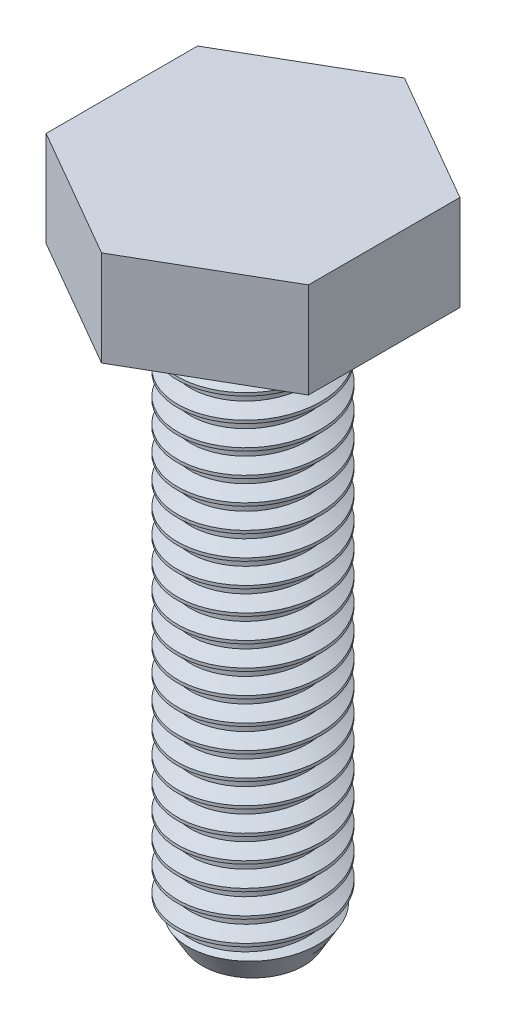
SolidWorks part; units mm, degrees
material "Alloy Steel"
ref_plane "Front Plane" through (0, 0, 0) normal (0, 0, 1) x (1, 0, 0)
ref_plane "Top Plane" through (0, 0, 0) normal (0, 1, 0) x (1, 0, 0)
ref_plane "Right Plane" through (0, 0, 0) normal (1, 0, 0) x (0, 0, -1)
sketch "Sketch1" plane through (0, 0, 0) normal (0, 0, 1) x (1, 0, 0)
  line L0 (0, 14) -> (2.75, 14)
  line L1 (2.75, 14) -> (2.75, 12)
  line L2 (2.75, 12) -> (1.5, 12)
  line L3 (1.5, 12) -> (1.5, 0.75)
  line L4 (1.067, 0) -> (0, 0)
  line L5 (0, 0) -> (0, 14)
  line L6 (1.5, 0.75) -> (1.067, 0)
  point P4 (1.5, 0)
  point P5 (2.125, 12)
  dimension "D1" = 2.75
  dimension "D2" = 2
  dimension "D3" = 1.5
  dimension "D4" = 12
  dimension "D5" = 0.75
  dimension "D6" = 30
revolve "Revolve1" add sketch "Sketch1" angle 360 about L5
sketch "Sketch2" plane through (0, 14, 0) normal (0, 1, 0) x (1, 0, 0)
  line L1 (0, 3.1754) -> (-2.75, 1.5877)
  line L2 (-2.75, 1.5877) -> (-2.75, -1.5877)
  line L3 (-2.75, -1.5877) -> (0, -3.1754)
  line L4 (0, -3.1754) -> (2.75, -1.5877)
  line L5 (2.75, -1.5877) -> (2.75, 1.5877)
  line L6 (2.75, 1.5877) -> (0, 3.1754)
  circle A0 centre (0, 0) radius 2.75 construction
  circle A1 centre (0, 0) radius 2.75 construction
extrude "Boss-Extrude1" add sketch "Sketch2" against normal blind 2
thread "Thread1" pitch 0.5 start angle 0, offset 0, length 0, pitch 0.5, diameter 3
ref_plane "Plane1" through (1.5, 0, 0) normal (0, 0, 1) x (1, 0, 0)
sketch "Thread Profile1" plane through (1.5, 0, 0) normal (0, 0, 1) x (1, 0, 0)
  line L0 (0, 0) -> (0, 0.5) construction
  line L11 (0, 0) -> (0, 0.4375)
  line L12 (0, 0.4375) -> (-0.2706, 0.2812)
  line L13 (-0.2706, 0.2812) -> (-0.2706, 0.1562)
  line L15 (-0.2706, 0.1562) -> (0, 0)
  line L17 (-0.2706, 0.2187) -> (0, 0.2187) construction
  point P2 (0, 0)
  dimension "Pitch" = 0.5
  dimension "Profile_Angle" = 60
  dimension "Profile_Land" = 0.125
  dimension "Profile_Height" = 0.2706
